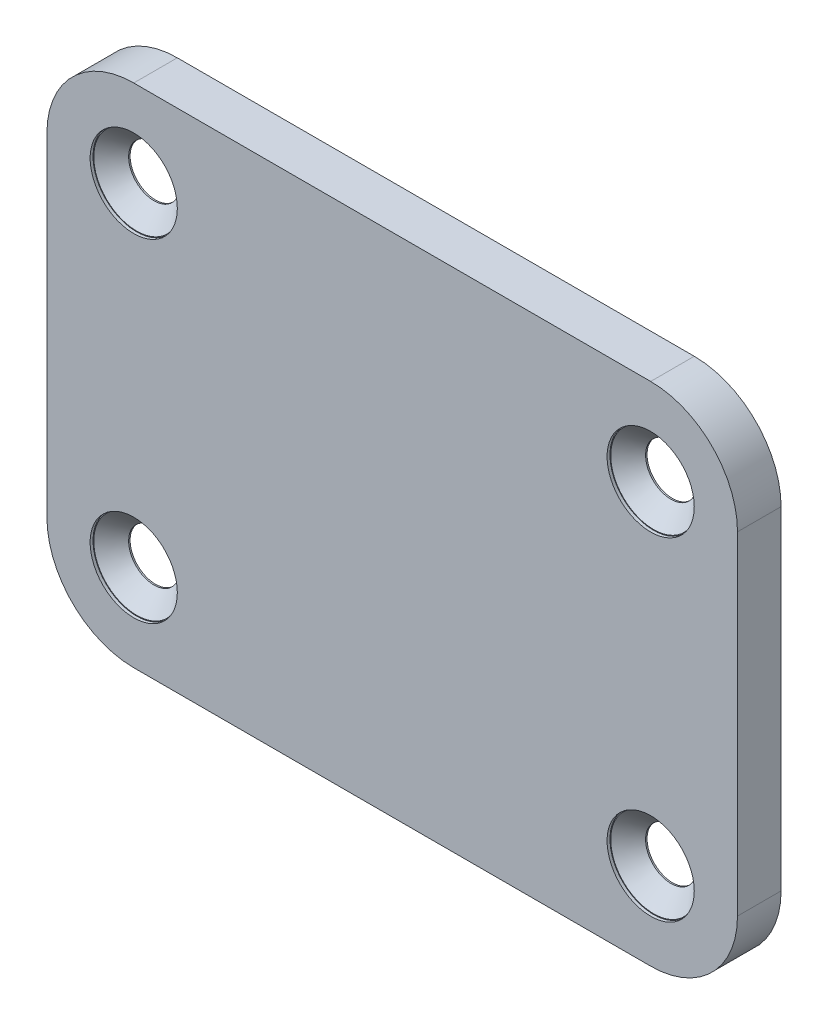
SolidWorks part; units mm, degrees
ref_plane "Front Plane" through (0, 0, 0) normal (0, 0, 1) x (1, 0, 0)
ref_plane "Top Plane" through (0, 0, 0) normal (0, 1, 0) x (1, 0, 0)
ref_plane "Right Plane" through (0, 0, 0) normal (1, 0, 0) x (0, 0, -1)
sketch "Sketch1" plane through (0, 0, 0) normal (0, 0, 1) x (1, 0, 0)
  line L4 (-17.7875, 11.45) -> (-17.7875, 17.425) construction
  line L5 (23.7625, -17.425) -> (-23.7625, -17.425)
  line L6 (23.7625, -17.425) -> (23.7625, 17.425)
  line L7 (23.7625, 17.425) -> (-23.7625, 17.425)
  line L8 (-22.275, 11.45) -> (-22.275, -11.45)
  line L9 (-18.1222, -15.925) -> (18.1222, -15.925)
  line L10 (22.275, -11.45) -> (22.275, 11.45)
  line L11 (18.1222, 15.925) -> (-18.1222, 15.925)
  line L12 (-22.275, 11.45) -> (-22.275, -11.45)
  line L13 (-18.1222, -15.925) -> (18.1222, -15.925)
  line L14 (22.275, -11.45) -> (22.275, 11.45)
  line L15 (18.1222, 15.925) -> (-18.1222, 15.925)
  line L16 (-23.7625, -17.425) -> (-23.7625, 17.425)
  line L17 (23.7625, -17.425) -> (-23.7625, 17.425) construction
  line L18 (23.7625, 17.425) -> (-23.7625, -17.425) construction
  line L19 (-17.7875, 11.45) -> (-23.7625, 11.45) construction
  circle A0 centre (-17.7875, 11.45) radius 1.75
  circle A1 centre (-17.7875, 11.45) radius 1.75 construction
  circle A2 centre (17.7875, 11.45) radius 1.75
  circle A3 centre (17.7875, 11.45) radius 1.75 construction
  circle A4 centre (17.7875, -11.45) radius 1.75
  circle A5 centre (17.7875, -11.45) radius 1.75 construction
  circle A6 centre (-17.7875, -11.45) radius 1.75
  circle A7 centre (-17.7875, -11.45) radius 1.75 construction
  circle A8 centre (-17.7875, 11.45) radius 5.975
  circle A9 centre (17.7875, 11.45) radius 5.975
  circle A10 centre (17.7875, -11.45) radius 5.975
  circle A11 centre (-17.7875, -11.45) radius 5.975
  arc A16 (22.275, 11.45) -> (18.1222, 15.925) centre (17.7875, 11.45) ccw
  arc A17 (22.275, 11.45) -> (18.1222, 15.925) centre (17.7875, 11.45) ccw
  arc A18 (-18.1222, 15.925) -> (-22.275, 11.45) centre (-17.7875, 11.45) ccw
  arc A19 (-18.1222, 15.925) -> (-22.275, 11.45) centre (-17.7875, 11.45) ccw
  arc A20 (-22.275, -11.45) -> (-18.1222, -15.925) centre (-17.7875, -11.45) ccw
  arc A21 (-22.275, -11.45) -> (-18.1222, -15.925) centre (-17.7875, -11.45) ccw
  arc A22 (18.1222, -15.925) -> (22.275, -11.45) centre (17.7875, -11.45) ccw
  arc A23 (18.1222, -15.925) -> (22.275, -11.45) centre (17.7875, -11.45) ccw
  point P24 (0, 0)
  dimension "D2" = 1.5
  dimension "D1" = 0.25
extrude "Boss-Extrude1" add sketch "Sketch1" along normal blind 1.5 contours L15 A19 L12 A8 A0 | A19 L15 A8 L12 | A11 L12 A8 L16 | A21 L12 A11 L13 | L12 A21 L13 A11 A6 | A11 L13 A10 L14 A9 L15 A8 L12 | A9 L7 A8 L15 | A17 L14 A9 L15 | L14 A17 L15 A9 A2 | L13 A23 L14 A10 A4 | A10 L6 A9 L14 | A23 L13 A10 L14 | A11 L5 A10 L13 region at (0, -16.7008, 0) region at (15.7203, -16.9061, 0) region at (23.0626, 0, 0) region at (-21.9132, -15.5757, 0) region at (13.6736, -7.3231, 0) region at (0, 0, 0) region at (23.2469, 9.3915, 0) region at (-23.0626, 0, 0) region at (-15.9753, -15.7771, 0) region at (0, 16.7008, 0) region at (13.6736, 7.3231, 0) region at (-21.9132, 15.5757, 0) region at (-22.1271, 9.4775, 0)
sketch "Sketch2" plane through (0, 0, 0) normal (0, 0, -1) x (-1, 0, 0)
  line L0 (17.7875, 15.925) -> (-17.7875, 15.925)
  line L1 (-22.2625, 11.45) -> (-22.2625, -11.45)
  line L2 (-17.7875, -15.925) -> (17.7875, -15.925)
  line L3 (22.2625, -11.45) -> (22.2625, 11.45)
  line L4 (-17.7875, -17.425) -> (17.7875, -17.425)
  line L5 (-23.7625, 11.45) -> (-23.7625, -11.45)
  line L6 (17.7875, 17.425) -> (-17.7875, 17.425)
  line L7 (23.7625, -11.45) -> (23.7625, 11.45)
  line L8 (-17.7875, -17.425) -> (17.7875, -17.425)
  line L9 (-23.7625, 11.45) -> (-23.7625, -11.45)
  line L10 (17.7875, 17.425) -> (-17.7875, 17.425)
  line L11 (23.7625, -11.45) -> (23.7625, 11.45)
  arc A0 (22.2625, 11.45) -> (17.7875, 15.925) centre (17.7875, 11.45) ccw
  arc A1 (-17.7875, 15.925) -> (-22.2625, 11.45) centre (-17.7875, 11.45) ccw
  arc A2 (-22.2625, -11.45) -> (-17.7875, -15.925) centre (-17.7875, -11.45) ccw
  arc A3 (17.7875, -15.925) -> (22.2625, -11.45) centre (17.7875, -11.45) ccw
  arc A4 (-23.7625, -11.45) -> (-17.7875, -17.425) centre (-17.7875, -11.45) ccw
  arc A5 (-17.7875, 17.425) -> (-23.7625, 11.45) centre (-17.7875, 11.45) ccw
  arc A6 (23.7625, 11.45) -> (17.7875, 17.425) centre (17.7875, 11.45) ccw
  arc A7 (17.7875, -17.425) -> (23.7625, -11.45) centre (17.7875, -11.45) ccw
  arc A8 (-23.7625, -11.45) -> (-17.7875, -17.425) centre (-17.7875, -11.45) ccw
  arc A9 (-17.7875, 17.425) -> (-23.7625, 11.45) centre (-17.7875, 11.45) ccw
  arc A10 (23.7625, 11.45) -> (17.7875, 17.425) centre (17.7875, 11.45) ccw
  arc A11 (17.7875, -17.425) -> (23.7625, -11.45) centre (17.7875, -11.45) ccw
  dimension "D2" = 1.5
  dimension "D1" = 0
extrude "Boss-Extrude2" add sketch "Sketch2" along normal blind 1.5
sketch "Sketch3" plane through (0, 0, 0) normal (0, 0, -1) x (-1, 0, 0)
  line L0 (-22.2625, 11.45) -> (-22.2625, -11.45) construction
  line L1 (22.2625, -6.975) -> (-22.2625, -6.975)
  line L2 (22.2625, -6.975) -> (22.2625, 6.975)
  line L3 (22.2625, 6.975) -> (-22.2625, 6.975)
  line L4 (-22.2625, -6.975) -> (-22.2625, 6.975)
  line L5 (22.2625, -6.975) -> (-22.2625, 6.975) construction
  line L6 (22.2625, 6.975) -> (-22.2625, -6.975) construction
  line L7 (17.7875, 15.925) -> (-17.7875, 15.925) construction
  line L8 (-13.3125, -15.925) -> (13.3125, -15.925)
  line L9 (-13.3125, -15.925) -> (-13.3125, 15.925)
  line L10 (-13.3125, 15.925) -> (13.3125, 15.925)
  line L11 (13.3125, -15.925) -> (13.3125, 15.925)
  line L12 (-13.3125, -15.925) -> (13.3125, 15.925) construction
  line L13 (-13.3125, 15.925) -> (13.3125, -15.925) construction
  circle A0 centre (17.7875, 11.45) radius 4.475
  arc A1 (22.2625, 11.45) -> (17.7875, 15.925) centre (17.7875, 11.45) ccw construction
  circle A2 centre (-17.7875, 11.45) radius 4.475
  circle A3 centre (-17.7875, -11.45) radius 4.475
  circle A4 centre (17.7875, -11.45) radius 4.475
  point P0 (0, 0)
  point P8 (0, 0)
  line M3 (22.2625, -11.45) -> (22.2625, 11.45)
  line M5 (17.7875, 15.925) -> (-17.7875, 15.925)
  line M7 (-22.2625, 11.45) -> (-22.2625, -11.45)
  line M9 (-17.7875, -15.925) -> (17.7875, -15.925)
extrude "Cut-Extrude1" cut sketch "Sketch3" against normal blind 0.5 contours A2 L3 L9 | L1 L9 L3 M7 | L3 L11 L9 M5 | A0 L11 L3 | L11 L1 L3 M3 | A4 L1 L11 | L11 L1 L9 M9 | L1 L11 L3 L9 region at (-17.7875, 0, 0) region at (-14.3121, -7.9746, 0) region at (0, -11.45, 0) region at (0, 0, 0) region at (-14.3121, 7.9746, 0) region at (17.7875, 0, 0) region at (0, 11.45, 0) region at (14.3121, 7.9746, 0)
sketch "Sketch4" plane through (0, 0, 1.5) normal (0, 0, 1) x (1, 0, 0)
  circle A0 centre (-17.7875, 11.45) radius 3
  circle A1 centre (17.7875, 11.45) radius 3
  circle A2 centre (17.7875, -11.45) radius 3
  circle A3 centre (-17.7875, -11.45) radius 3
  dimension "D1" = 6
extrude "Cut-Extrude2" cut sketch "Sketch4" against normal blind 0.2
chamfer "Chamfer1" distance 1.2 angle 45 4 edges at (-16.0375, -11.45, 1.3) (19.5375, -11.45, 1.3) (19.5375, 11.45, 1.3) (-16.0375, 11.45, 1.3)
